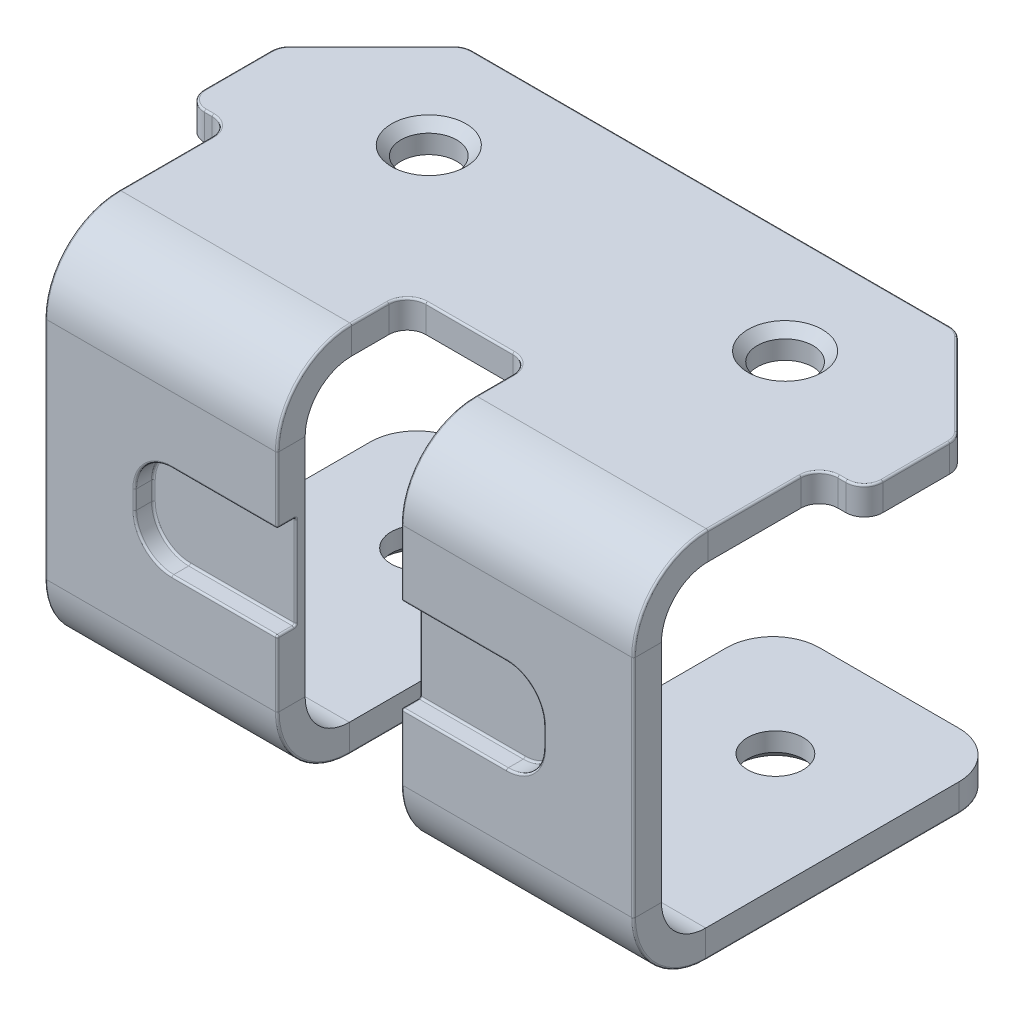
SolidWorks part; units mm, degrees
note: The reader was unsure of these and kept them because the rebuilt part matched: flange length of "Edge-Flange1", "Edge-Flange2".
material "moto_black"
ref_plane "Front Plane" through (0, 0, 0) normal (0, 0, 1) x (1, 0, 0)
ref_plane "Top Plane" through (0, 0, 0) normal (0, 1, 0) x (1, 0, 0)
ref_plane "Right Plane" through (0, 0, 0) normal (1, 0, 0) x (0, 0, -1)
sketch "Sketch2" plane through (0, 0, 0) normal (0, 1, 0) x (1, 0, 0)
  line L2 (-36.5, -4) -> (-36.5, 16)
  line L3 (-36.5, 16) -> (36.5, 16)
  line L4 (36.5, -4) -> (36.5, 16)
  line L7 (6.6693, -10) -> (6.6693, -24)
  line L9 (-31.6693, -4) -> (-31.6693, -24)
  line L10 (-31.6693, -24) -> (-6.6693, -24)
  line L11 (-6.6693, -10) -> (-6.6693, -24)
  line L12 (31.6693, -24) -> (6.6693, -24)
  line L13 (31.6693, -4) -> (31.6693, -24)
  line L15 (-6.6693, -10) -> (6.6693, -10)
  line L17 (36.5, -4) -> (31.6693, -4)
  line L18 (-36.5, -4) -> (-31.6693, -4)
  point P0 (0, 0)
  dimension "D1" = 73
  dimension "D2" = 20
  dimension "D3" = 25
  dimension "D4" = 20
  dimension "D5" = 20
  dimension "D6" = 20
base flange "Base-Flange2" sketch "Sketch2" thickness 3 reverse thickness direction no parameters "D1"=0.7366
edge flange "Edge-Flange1" sketch "Sketch21" flange profiles "Sketch21", "Sketch22" flange angle 90 flange length 40 flange position material inside bend radius 5 thickness 3 relief rectangular parameters "D6"=10, "D8"=1
sketch "Sketch21" plane through (0, -3, 24) normal (0, 0, 1) x (-1, 0, 0)
  line L0 (-6.6693, 0) -> (-31.6693, 0) construction
  line L1 (-6.6693, 0) -> (-31.6693, 0)
  line L2 (-31.6693, 0) -> (-31.6693, 37)
  line L3 (-31.6693, 37) -> (-6.6693, 37)
  line L4 (-6.6693, 37) -> (-6.6693, 0)
sketch "Sketch22" plane through (0, -3, 24) normal (0, 0, 1) x (-1, 0, 0)
  line L0 (31.6693, 0) -> (6.6693, 0) construction
  line L1 (31.6693, 0) -> (6.6693, 0)
  line L2 (6.6693, 0) -> (6.6693, 37)
  line L3 (6.6693, 37) -> (31.6693, 37)
  line L4 (31.6693, 37) -> (31.6693, 0)
bend "EdgeBend1" bend radius 5 bend angle 90 parameters "D5"=1
bend "EdgeBend2" bend radius 5 bend angle 90 parameters "D5"=2
edge flange "Edge-Flange2" sketch "Sketch27" flange profiles "Sketch27", "Sketch28" flange angle 90 flange length 40 flange position material inside bend radius 4.76 thickness 3 relief rectangular parameters "D6"=10, "D8"=1
sketch "Sketch27" plane through (0, -40, 21) normal (0, -1, 0) x (-1, 0, 0)
  line L0 (-6.6693, 0) -> (-31.6693, 0) construction
  line L1 (-6.6693, 0) -> (-31.6693, 0)
  line L2 (-31.6693, 0) -> (-31.6693, 37)
  line L3 (-31.6693, 37) -> (-6.6693, 37)
  line L4 (-6.6693, 37) -> (-6.6693, 0)
sketch "Sketch28" plane through (0, -40, 21) normal (0, -1, 0) x (-1, 0, 0)
  line L0 (31.6693, 0) -> (6.6693, 0) construction
  line L1 (31.6693, 0) -> (6.6693, 0)
  line L2 (6.6693, 0) -> (6.6693, 37)
  line L3 (6.6693, 37) -> (31.6693, 37)
  line L4 (31.6693, 37) -> (31.6693, 0)
bend "EdgeBend3" bend radius 4.76 bend angle 90 parameters "D5"=3
bend "EdgeBend4" bend radius 4.76 bend angle 90 parameters "D5"=4
chamfer "Chamfer1" distance 10 angle 45 2 edges at (-36.5, -1.5, -16) (36.5, -1.5, -16)
fillet "Fillet1" radius 2 6 edges at (-36.5, -1.5, 4) (-36.5, -1.5, -6) (-26.5, -1.5, -16) (36.5, -1.5, 4) (36.5, -1.5, -6) (26.5, -1.5, -16)
fillet "Fillet2" radius 2 4 edges at (-31.6693, -1.5, 4) (-6.6693, -1.5, 10) (6.6693, -1.5, 10) (31.6693, -1.5, 4)
fillet "Fillet3" radius 5 4 edges at (-31.6693, -38.5, -16) (-6.6693, -38.5, -16) (6.6693, -38.5, -16) (31.6693, -38.5, -16)
sketch "Sketch29" plane through (0, 0, 0) normal (0, 1, 0) x (1, 0, 0)
  line L14 (-19.1693, -16) -> (-19.1693, 16)
  line L15 (0, -10) -> (0, -14.6648)
  line L28 (-36.5, 5.1716) -> (-36.5, -2)
  line L29 (-34.5, -4) -> (-33.6693, -4)
  line L30 (-31.6693, -6) -> (-31.6693, -16)
  line L31 (-31.6693, -16) -> (-6.6693, -16)
  line L32 (-6.6693, -16) -> (-6.6693, -12)
  line L33 (-4.6693, -10) -> (4.6693, -10)
  line L34 (6.6693, -12) -> (6.6693, -16)
  line L35 (6.6693, -16) -> (31.6693, -16)
  line L36 (31.6693, -16) -> (31.6693, -6)
  line L37 (33.6693, -4) -> (34.5, -4)
  line L38 (36.5, -2) -> (36.5, 5.1716)
  line L39 (35.9142, 6.5858) -> (27.0858, 15.4142)
  line L40 (25.6716, 16) -> (-25.6716, 16)
  line L41 (-27.0858, 15.4142) -> (-35.9142, 6.5858)
  line L42 (-36.5, 5.1716) -> (-36.5, -2)
  line L43 (-34.5, -4) -> (-33.6693, -4)
  line L44 (-31.6693, -6) -> (-31.6693, -16)
  line L45 (-31.6693, -16) -> (-6.6693, -16)
  line L46 (-6.6693, -16) -> (-6.6693, -12)
  line L47 (-4.6693, -10) -> (4.6693, -10)
  line L48 (6.6693, -12) -> (6.6693, -16)
  line L49 (6.6693, -16) -> (31.6693, -16)
  line L50 (31.6693, -16) -> (31.6693, -6)
  line L51 (33.6693, -4) -> (34.5, -4)
  line L52 (36.5, -2) -> (36.5, 5.1716)
  line L53 (35.9142, 6.5858) -> (27.0858, 15.4142)
  line L54 (25.6716, 16) -> (-25.6716, 16)
  line L55 (-27.0858, 15.4142) -> (-35.9142, 6.5858)
  circle A10 centre (-19.1693, 4.8038) radius 3
  circle A11 centre (19.1693, 4.8038) radius 3
  arc A20 (-36.5, -2) -> (-34.5, -4) centre (-34.5, -2) ccw
  arc A21 (-31.6693, -6) -> (-33.6693, -4) centre (-33.6693, -6) ccw
  arc A22 (-4.6693, -10) -> (-6.6693, -12) centre (-4.6693, -12) ccw
  arc A23 (6.6693, -12) -> (4.6693, -10) centre (4.6693, -12) ccw
  arc A24 (33.6693, -4) -> (31.6693, -6) centre (33.6693, -6) ccw
  arc A25 (34.5, -4) -> (36.5, -2) centre (34.5, -2) ccw
  arc A26 (36.5, 5.1716) -> (35.9142, 6.5858) centre (34.5, 5.1716) ccw
  arc A27 (27.0858, 15.4142) -> (25.6716, 16) centre (25.6716, 14) ccw
  arc A28 (-25.6716, 16) -> (-27.0858, 15.4142) centre (-25.6716, 14) ccw
  arc A29 (-35.9142, 6.5858) -> (-36.5, 5.1716) centre (-34.5, 5.1716) ccw
  arc A30 (-36.5, -2) -> (-34.5, -4) centre (-34.5, -2) ccw
  arc A31 (-31.6693, -6) -> (-33.6693, -4) centre (-33.6693, -6) ccw
  arc A32 (-4.6693, -10) -> (-6.6693, -12) centre (-4.6693, -12) ccw
  arc A33 (6.6693, -12) -> (4.6693, -10) centre (4.6693, -12) ccw
  arc A34 (33.6693, -4) -> (31.6693, -6) centre (33.6693, -6) ccw
  arc A35 (34.5, -4) -> (36.5, -2) centre (34.5, -2) ccw
  arc A36 (36.5, 5.1716) -> (35.9142, 6.5858) centre (34.5, 5.1716) ccw
  arc A37 (27.0858, 15.4142) -> (25.6716, 16) centre (25.6716, 14) ccw
  arc A38 (-25.6716, 16) -> (-27.0858, 15.4142) centre (-25.6716, 14) ccw
  arc A39 (-35.9142, 6.5858) -> (-36.5, 5.1716) centre (-34.5, 5.1716) ccw
  dimension "D2" = 6
  dimension "D1" = 0
extrude "Cut-Extrude1" cut sketch "Sketch29" against normal blind 18 contours L14 A10 | A11
sketch "Sketch30" plane through (0, -40, 0) normal (0, -1, 0) x (1, 0, 0)
  line L4 (0, 0) -> (0, 18.3867)
  line L8 (-31.6693, 16.24) -> (-31.6693, -11)
  line L9 (-26.6693, -16) -> (-11.6693, -16)
  line L10 (-6.6693, -11) -> (-6.6693, 16.24)
  line L11 (-6.6693, 16.24) -> (-31.6693, 16.24)
  line L12 (-31.6693, 16.24) -> (-31.6693, -11)
  line L13 (-26.6693, -16) -> (-11.6693, -16)
  line L14 (-6.6693, -11) -> (-6.6693, 16.24)
  line L15 (-6.6693, 16.24) -> (-31.6693, 16.24)
  circle A2 centre (-19.1693, -3.76) radius 3
  circle A3 centre (19.1693, -3.76) radius 3
  arc A4 (-31.6693, -11) -> (-26.6693, -16) centre (-26.6693, -11) ccw
  arc A5 (-11.6693, -16) -> (-6.6693, -11) centre (-11.6693, -11) ccw
  arc A6 (-31.6693, -11) -> (-26.6693, -16) centre (-26.6693, -11) ccw
  arc A7 (-11.6693, -16) -> (-6.6693, -11) centre (-11.6693, -11) ccw
  dimension "D2" = 20
  dimension "D1" = 0
extrude "Cut-Extrude2" cut sketch "Sketch30" against normal blind 18
chamfer "Chamfer2" distance 1 angle 45 4 edges at (19.1693, -40, -6.76) (-19.1693, -40, -6.76) (-19.1693, 0, -1.8038) (19.1693, 0, -1.8038)
sketch "Sketch32" plane through (0, 0, 24) normal (0, 0, 1) x (1, 0, 0)
  line L0 (-6.6693, -20.12) -> (6.6693, -20.12)
  line L1 (-6.6693, -32.24) -> (-6.6693, -8) construction
  line L2 (6.6693, -8) -> (6.6693, -32.24) construction
  line L3 (0, -20.12) -> (0, -13.3869)
  line L5 (-18, -25.12) -> (18, -25.12)
  line L6 (-22, -21.12) -> (-22, -19.12)
  line L7 (-18, -15.12) -> (18, -15.12)
  line L8 (22, -21.12) -> (22, -19.12)
  line L9 (-22, -25.12) -> (22, -15.12) construction
  line L10 (-22, -15.12) -> (22, -25.12) construction
  arc A0 (22, -19.12) -> (18, -15.12) centre (18, -19.12) ccw
  arc A1 (22, -21.12) -> (18, -25.12) centre (18, -21.12) cw
  arc A2 (-22, -21.12) -> (-18, -25.12) centre (-18, -21.12) ccw
  arc A3 (-18, -15.12) -> (-22, -19.12) centre (-18, -19.12) ccw
  dimension "D3" = 4
  dimension "D1" = 10
  dimension "D2" = 44
extrude "Cut-Extrude3" cut sketch "Sketch32" against normal blind 2
fillet "Fillet4" radius 0.2 72 edges at (31.6693, -20.12, 24) (-6.6693, -28.68, 24) (31.6693, -37.7271, 21.7271) (6.6693, -37.7271, 21.7271) (6.6693, -40, 2.62) (-6.6693, -37.7271, 21.7271) (-31.6693, -37.7271, 21.7271) (-31.6693, -40, 2.62) (-36.5, 0, -1.5858) (0, 0, -16) (-31.5, 0, -11) (-34.0847, 0, 4) (36.5, 0, -1.5858) (31.5, 0, -11) (26.4369, 0, -15.8478) (36.3478, 0, -5.9369) (35.9142, 0, 3.4142) (-26.4369, 0, -15.8478) (-36.3478, 0, -5.9369) (-35.9142, 0, 3.4142) (-31.6693, 0, 11) (0, 0, 10) (6.6693, 0, 14) (34.0847, 0, 4) (-32.2551, 0, 4.5858) (-6.0835, 0, 10.5858) (6.0835, 0, 10.5858) (32.2551, 0, 4.5858) (-19.1693, -40, -16) (-6.6693, -40, 2.62) (-8.1338, -40, -14.5355) (-30.2049, -40, -14.5355) (19.1693, -40, -16) (31.6693, -40, 2.62) (30.2049, -40, -14.5355) (8.1338, -40, -14.5355) (31.6693, 0, 11) (-6.6693, 0, 14) (6.6693, -28.68, 24) (12.3347, -15.12, 24) (12.3347, -25.12, 24) (6.6693, -20.12, 22) (-6.6693, -11.56, 24) (-22, -20.12, 22) (-12.3347, -15.12, 22) (12.3347, -15.12, 22) (20.8284, -23.9484, 22) (-12.3347, -25.12, 24) (-20.8284, -16.2916, 24) (-20.8284, -23.9484, 24) (22, -20.12, 24) (20.8284, -16.2916, 24) (-12.3347, -25.12, 22) (-6.6693, -25.12, 23) (6.6693, -25.12, 23) (12.3347, -25.12, 22) (-12.3347, -15.12, 24) (20.8284, -16.2916, 22) (22, -20.12, 22) (20.8284, -23.9484, 24) (-20.8284, -23.9484, 22) (-22, -20.12, 24) (-20.8284, -16.2916, 22) (-6.6693, -15.12, 23) (6.6693, -15.12, 23) (-6.6693, -20.12, 22) (31.6693, -2.3431, 21.6569) (6.6693, -2.3431, 21.6569) (6.6693, -11.56, 24) (-6.6693, -2.3431, 21.6569) (-31.6693, -2.3431, 21.6569) (-31.6693, -20.12, 24)
sketch "Bend-Lines3" [suppressed] plane through (0, 0, 0) normal (0, 1, 0) x (1, 0, 0)
sketch "Bounding-Box3" [suppressed] plane through (0, 0, 0) normal (0, 1, 0) x (1, 0, 0)
sheet metal parameters "Sheet-Metal2" thickness 3 parameters "D1"=0.7366
flat pattern "Flat-Pattern2" [suppressed]
sketch "Bend-Lines4" plane through (0, 0, 0) normal (0, 1, 0) x (1, 0, 0)
sketch3d "Bounding-Box4" [suppressed]
  line L0 (-36.5, 10, 0) -> (36.5, 10, 0) construction
  line L1 (-36.5, -24, 0) -> (36.5, -24, 0) construction
  line L2 (-36.5, 10, 0) -> (-36.5, -24, 0) construction
  line L3 (36.5, 10, 0) -> (36.5, -24, 0) construction
sheet metal parameters "Sheet-Metal3" thickness 3 parameters "D1"=0.7366
flat pattern "Flat-Pattern2"
sketch "Bend-Lines4" plane through (0, 0, 0) normal (0, 1, 0) x (1, 0, 0)
  line L0 (-31.6693, -21.1051) -> (-6.6693, -21.1051) construction
  line L1 (6.6693, -21.1051) -> (31.6693, -21.1051) construction
  line L2 (-31.6693, -21.1051) -> (-6.6693, -21.1051) construction
  line L3 (6.6693, -21.1051) -> (31.6693, -21.1051) construction
sketch3d "Bounding-Box4" [suppressed]
  line L0 (36.5, 10, 0) -> (-36.5, 10, 0) construction
  line L1 (36.5, -46.2102, 0) -> (-36.5, -46.2102, 0) construction
  line L2 (36.5, 10, 0) -> (36.5, -46.2102, 0) construction
  line L3 (-36.5, 10, 0) -> (-36.5, -46.2102, 0) construction
bend of the flat pattern "Flatten-<EdgeBend1>1"
bend of the flat pattern "Flatten-<EdgeBend2>1"
sheet metal parameters "Sheet-Metal4" thickness 3 parameters "D1"=0.7366
flat pattern "Flat-Pattern2"
sketch "Bend-Lines4" plane through (0, 0, 0) normal (0, 1, 0) x (1, 0, 0)
  line L0 (-31.6693, -21.1051) -> (-6.6693, -21.1051) construction
  line L1 (6.6693, -21.1051) -> (31.6693, -21.1051) construction
  line L2 (-31.6693, -21.1051) -> (-6.6693, -21.1051) construction
  line L3 (6.6693, -21.1051) -> (31.6693, -21.1051) construction
  line L4 (-31.6693, -55.3668) -> (-6.6693, -55.3668) construction
  line L5 (6.6693, -55.3668) -> (31.6693, -55.3668) construction
  line L6 (-31.6693, -55.3668) -> (-6.6693, -55.3668) construction
  line L7 (6.6693, -55.3668) -> (31.6693, -55.3668) construction
sketch3d "Bounding-Box4" [suppressed]
  line L0 (36.5, -84.2599, 0) -> (36.5, 16, 0) construction
  line L1 (-36.5, -84.26, 0) -> (-36.5, 16, 0) construction
  line L2 (36.5, -84.2599, 0) -> (-36.5, -84.26, 0) construction
  line L3 (36.5, 16, 0) -> (-36.5, 16, 0) construction
bend of the flat pattern "Flatten-<EdgeBend1>1"
bend of the flat pattern "Flatten-<EdgeBend2>1"
bend of the flat pattern "Flatten-<EdgeBend3>1"
bend of the flat pattern "Flatten-<EdgeBend4>1"
sheet metal parameters "Sheet-Metal5" thickness 3 parameters "D1"=0.7366
flat pattern "Flat-Pattern2"
sketch "Bend-Lines4" plane through (0, 0, 0) normal (0, 1, 0) x (1, 0, 0)
  line L0 (-31.6693, -21.1051) -> (-6.6693, -21.1051) construction
  line L1 (6.6693, -21.1051) -> (31.6693, -21.1051) construction
  line L2 (-31.6693, -21.1051) -> (-6.6693, -21.1051) construction
  line L3 (6.6693, -21.1051) -> (31.6693, -21.1051) construction
  line L4 (-31.6693, -55.3668) -> (-6.6693, -55.3668) construction
  line L5 (6.6693, -55.3668) -> (31.6693, -55.3668) construction
  line L6 (-31.6693, -55.3668) -> (-6.6693, -55.3668) construction
  line L7 (6.6693, -55.3668) -> (31.6693, -55.3668) construction
sketch3d "Bounding-Box4" [suppressed]
  line L0 (36.5, -84.2599, 0) -> (36.5, 16, 0) construction
  line L1 (-36.5, -84.26, 0) -> (-36.5, 16, 0) construction
  line L2 (36.5, -84.2599, 0) -> (-36.5, -84.26, 0) construction
  line L3 (36.5, 16, 0) -> (-36.5, 16, 0) construction
bend of the flat pattern "Flatten-<EdgeBend1>1"
bend of the flat pattern "Flatten-<EdgeBend2>1"
bend of the flat pattern "Flatten-<EdgeBend3>1"
bend of the flat pattern "Flatten-<EdgeBend4>1"
sheet metal parameters "Sheet-Metal6" thickness 3 parameters "D1"=0.7366
flat pattern "Flat-Pattern2"
sketch "Bend-Lines4" plane through (0, 0, 0) normal (0, 1, 0) x (1, 0, 0)
  line L0 (-31.6693, -21.1051) -> (-6.6693, -21.1051) construction
  line L1 (6.6693, -21.1051) -> (31.6693, -21.1051) construction
  line L2 (-31.6693, -21.1051) -> (-6.6693, -21.1051) construction
  line L3 (6.6693, -21.1051) -> (31.6693, -21.1051) construction
  line L4 (-31.6693, -55.3668) -> (-6.6693, -55.3668) construction
  line L5 (6.6693, -55.3668) -> (31.6693, -55.3668) construction
  line L6 (-31.6693, -55.3668) -> (-6.6693, -55.3668) construction
  line L7 (6.6693, -55.3668) -> (31.6693, -55.3668) construction
sketch3d "Bounding-Box4" [suppressed]
  line L0 (36.5, -92.5234, -3) -> (36.5, 16, -3) construction
  line L1 (-36.5, -92.5234, -3) -> (-36.5, 16, -3) construction
  line L2 (36.5, -92.5234, -3) -> (-36.5, -92.5234, -3) construction
  line L3 (36.5, 16, -3) -> (-36.5, 16, -3) construction
bend of the flat pattern "Flatten-<EdgeBend1>1"
bend of the flat pattern "Flatten-<EdgeBend2>1"
bend of the flat pattern "Flatten-<EdgeBend3>1"
bend of the flat pattern "Flatten-<EdgeBend4>1"
sheet metal parameters "Sheet-Metal7" thickness 3 parameters "D1"=0.7366
flat pattern "Flat-Pattern2"
sketch "Bend-Lines4" plane through (0, 0, 0) normal (0, 1, 0) x (1, 0, 0)
  line L0 (-31.4693, -21.1051) -> (-6.8693, -21.1051) construction
  line L1 (6.8693, -21.1051) -> (31.4693, -21.1051) construction
  line L2 (-31.4693, -21.1051) -> (-6.8693, -21.1051) construction
  line L3 (6.8693, -21.1051) -> (31.4693, -21.1051) construction
  line L4 (-31.4693, -55.3668) -> (-6.8693, -55.3668) construction
  line L5 (6.8693, -55.3668) -> (31.4693, -55.3668) construction
  line L6 (-31.4693, -55.3668) -> (-6.8693, -55.3668) construction
  line L7 (6.8693, -55.3668) -> (31.4693, -55.3668) construction
sketch3d "Bounding-Box4" [suppressed]
  line L0 (36.5, 16, 0) -> (36.5, -92.5234, 0) construction
  line L1 (-36.5, 16, 0) -> (-36.5, -92.5234, 0) construction
  line L2 (36.5, 16, 0) -> (-36.5, 16, 0) construction
  line L3 (36.5, -92.5234, 0) -> (-36.5, -92.5234, 0) construction
bend of the flat pattern "Flatten-<EdgeBend1>1"
bend of the flat pattern "Flatten-<EdgeBend2>1"
bend of the flat pattern "Flatten-<EdgeBend3>1"
bend of the flat pattern "Flatten-<EdgeBend4>1"
